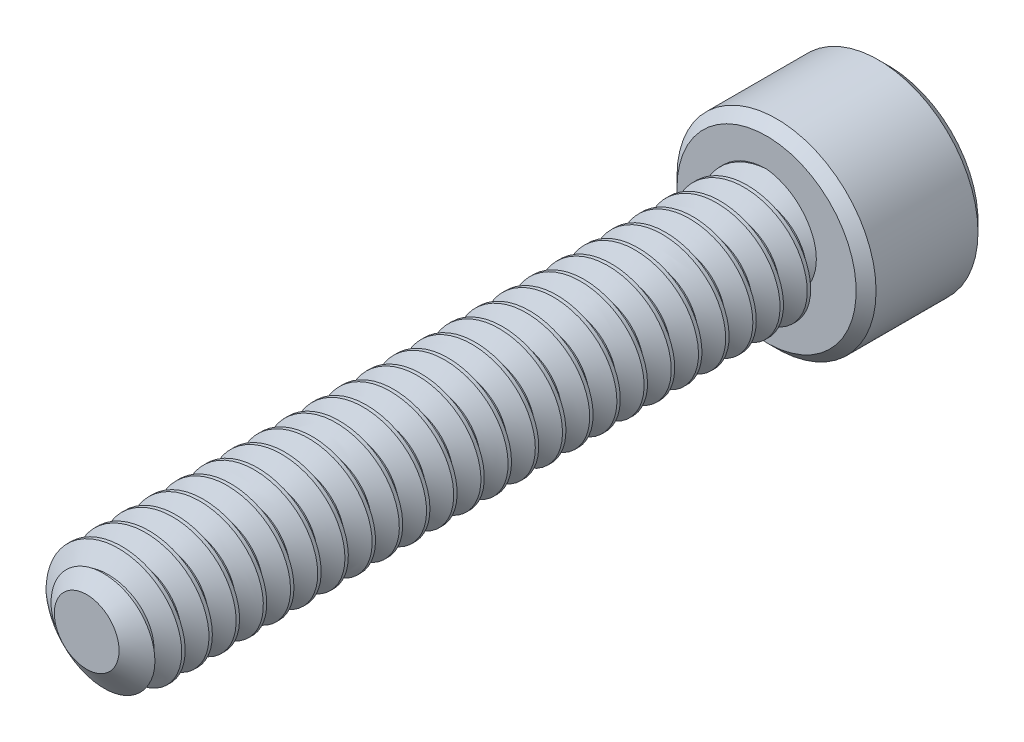
SolidWorks part; units mm, degrees
ref_plane "Front Plane" through (0, 0, 0) normal (0, 0, 1) x (1, 0, 0)
ref_plane "Top Plane" through (0, 0, 0) normal (0, 1, 0) x (1, 0, 0)
ref_plane "Right Plane" through (0, 0, 0) normal (1, 0, 0) x (0, 0, -1)
sketch "Sketch1" plane through (0, 0, 0) normal (0, 0, 1) x (1, 0, 0)
  circle A0 centre (0, 0) radius 1.4224
  dimension "OD" = 2.8448
extrude "Extrude1" add sketch "Sketch1" against normal blind 15.875
sketch "Sketch2" plane through (0, 0, 0) normal (0, 0, 1) x (1, 0, 0)
  circle A0 centre (0, 0) radius 1.4224 construction
  circle A1 centre (0, 0) radius 1.4224
curve "Helix/Spiral1" pitch 0.635 height 16.51 radius 1.4224 centre (0, 0, 0) axis (0, 0, -1) start towards (0, 1, 0) parameters "pitch"=0.635
sketch "Sketch3" plane through (0, 0, 0) normal (1, 0, 0) x (0, 0, -1)
  line L0 (-0.5556, 1.4224) -> (-0.3175, 1.01)
  line L1 (-0.3175, 1.01) -> (-0.2381, 1.01)
  line L2 (-0.2381, 1.01) -> (0, 1.4224)
  line L3 (-0.5556, 1.4224) -> (0, 1.4224)
  line L4 (-0.2778, 1.4224) -> (-0.2778, 1.01) construction
  line L5 (-0.4366, 1.2162) -> (-0.1191, 1.2162) construction
  line L6 (0, 1.4224) -> (0, -1.4224) construction
  dimension "D1" = 0.0794
  dimension "D2" = 0.3175
  dimension "D3" = 60
sweep "Cut-Sweep1" cut profiles "Sketch3" path "Helix/Spiral1"
sketch "Sketch4" plane through (0, 0, 0) normal (1, 0, 0) x (0, 0, -1)
  line L0 (0.4666, 1.4224) -> (0, 0.756)
  line L1 (0, 0.756) -> (0, 1.4224)
  line L2 (0.4666, 1.4224) -> (0, 1.4224)
  line L3 (-0.5556, 1.4224) -> (0, 1.4224) construction
  line L4 (0, 0) -> (7.0209, 0) construction
  dimension "D1" = 55
  dimension "D2" = 0.254
revolve "Cut-Revolve1" cut sketch "Sketch4" angle 360 about L4
sketch "Sketch5" plane through (0, 0, 0) normal (1, 0, 0) x (0, 0, -1)
  line L0 (15.875, -1.0232) -> (15.875, 1.0149) construction
  line L1 (15.875, 1.5494) -> (87.4327, 1.5494)
  line L2 (15.875, 1.5494) -> (15.875, 0)
  line L3 (15.875, 0) -> (87.3125, 0)
  line L4 (87.3125, 1.2192) -> (87.3125, 0)
  line L5 (87.4327, 1.5494) -> (87.3125, 1.2192)
  line L6 (0, 0) -> (9.9695, 0) construction
  point P3 (87.3125, 1.5494)
  point P10 (87.3125, 1.5494)
  dimension "D1" = 0.3302
  dimension "Thread min" = 87.3125
  dimension "D2" = 0.127
  dimension "D3" = 20
revolve "partially thread" [suppressed] add sketch "Sketch5" angle 360 about L6
sketch "Sketch6" plane through (0, 0, -15.875) normal (0, 0, -1) x (-1, 0, 0)
  circle A0 centre (0, 0) radius 2.3241
  dimension "head dia" = 4.6482
extrude "Extrude2" add sketch "Sketch6" along normal blind 2.8448
sketch "Sketch7" plane through (0, 0, -18.7198) normal (0, 0, -1) x (-1, 0, 0)
  line L1 (0, 1.3748) -> (-1.1906, 0.6874)
  line L2 (-1.1906, 0.6874) -> (-1.1906, -0.6874)
  line L3 (-1.1906, -0.6874) -> (0, -1.3748)
  line L4 (0, -1.3748) -> (1.1906, -0.6874)
  line L5 (1.1906, -0.6874) -> (1.1906, 0.6874)
  line L6 (1.1906, 0.6874) -> (0, 1.3748)
  circle A0 centre (0, 0) radius 1.1906 construction
  dimension "hex dia" = 2.3813
extrude "Cut-Extrude1" cut sketch "Sketch7" against normal blind 1.7859
sketch "Sketch8" plane through (0, 0, -18.7198) normal (0, 0, -1) x (-1, 0, 0)
  circle A0 centre (0, 0) radius 1.3748
extrude "Cut-Extrude2" cut sketch "Sketch8" against normal through all draft 45
chamfer "Chamfer1" distance 0.2324 angle 45 2 edges at (-2.3241, 0, -18.7198) (-2.3241, 0, -15.875)
sketch "Sketch9" plane through (0, 0, 0) normal (1, 0, 0) x (0, 0, -1)
  line L0 (0, 1.4224) -> (0, -1.4224) construction
  line L1 (3.4925, 1.4224) -> (3.4925, -1.4224) construction
  dimension "D1" = 3.4925
equation "\"D3@Helix/Spiral1\" = \"screw length@Extrude1\"+\"pitch@Helix/Spiral1\""
equation "\"D1@Sketch3\" = \"pitch@Helix/Spiral1\"*.125"
equation "\"D2@Sketch3\" = \"pitch@Helix/Spiral1\"*.5"
equation "\"D1@Cut-Extrude1\" = \"hex dia@Sketch7\"*.75"
equation "\"D1@Chamfer1\" = \"head dia@Sketch6\"*.05"
equation "\"D1@Sketch9\" = \"pitch@Helix/Spiral1\"*5.5"
